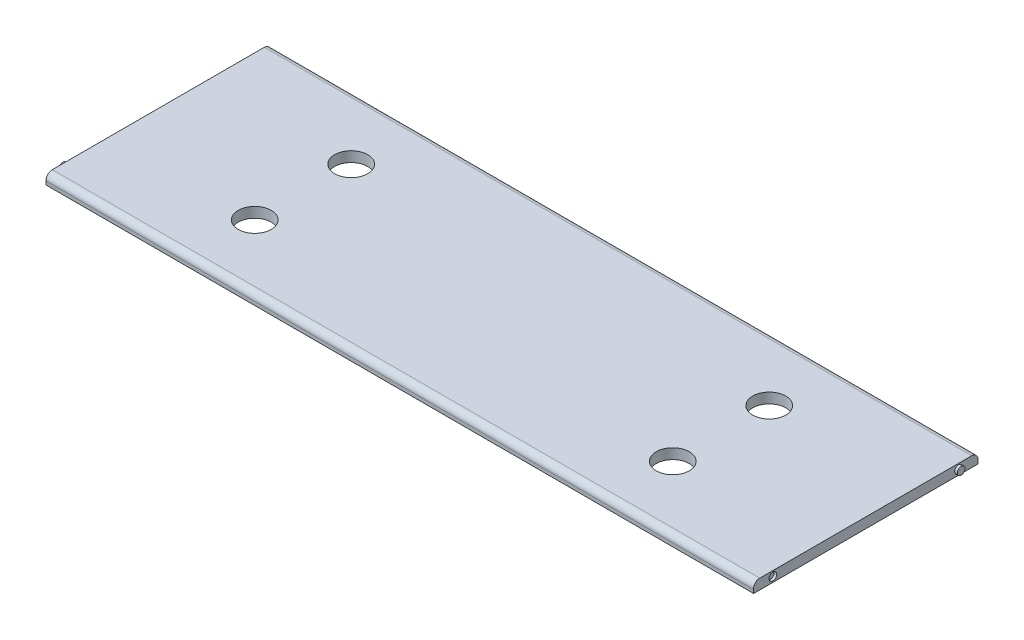
SolidWorks part; units mm, degrees
ref_plane "Front Plane" through (0, 0, 0) normal (0, 0, 1) x (1, 0, 0)
ref_plane "Top Plane" through (0, 0, 0) normal (0, 1, 0) x (1, 0, 0)
ref_plane "Right Plane" through (0, 0, 0) normal (1, 0, 0) x (0, 0, -1)
sketch "Sketch1" plane through (0, 0, 0) normal (0, 0, 1) x (1, 0, 0)
  line L0 (-247.65, 0) -> (247.65, 0) construction
  line L1 (0, 0) -> (0, 215.9) construction
  line L2 (69.85, 215.9) -> (-69.85, 215.9)
  line L3 (-247.65, 12.7) -> (-247.65, -12.7)
  line L4 (-247.65, -12.7) -> (-245.618, -12.7)
  line L5 (-245.618, -12.7) -> (-245.618, 12.7)
  line L6 (69.85, 213.868) -> (-69.85, 213.868)
  line L7 (247.65, 12.7) -> (247.65, -12.7)
  line L8 (247.65, -12.7) -> (245.618, -12.7)
  line L9 (245.618, -12.7) -> (245.618, 12.7)
  spline S0 degree 3 poles (-69.85, 215.9) (-159.8519, 215.9) (-247.65, 151.1387) (-247.65, 12.7) knots 0 0 0 0 1 1 1 1
  spline S1 degree 1 poles (-69.85, 213.868) (-245.618, 12.7) knots 0 0 1 1 construction
  spline S2 degree 3 poles (-69.85, 213.868) (-75.4039, 213.868) (-86.5291, 213.3675) (-108.5033, 210.3484) (-135.224, 202.7605) (-165.0781, 187.4572) (-187.3049, 169.4544) (-203.0081, 151.8427) (-213.6244, 137.0121) (-222.9564, 120.5424) (-230.8798, 102.4156) (-237.269, 82.6136) (-241.209, 64.7021) (-243.4667, 49.5177) (-244.6967, 37.7027) (-245.3224, 27.4898) (-245.5754, 19.121) (-245.618, 14.8317) (-245.618, 12.7) knots 0 0 0 0 0.0625 0.125 0.25 0.375 0.5 0.5625 0.625 0.6875 0.75 0.8125 0.875 0.90625 0.9375 0.96875 0.984375 1 1 1 1
  spline S3 degree 3 poles (247.65, 12.7) (247.65, 151.1387) (159.8519, 215.9) (69.85, 215.9) knots 0 0 0 0 1 1 1 1
  spline S4 degree 1 poles (245.618, 12.7) (69.85, 213.868) knots 0 0 1 1 construction
  spline S5 degree 3 poles (245.618, 12.7) (245.618, 14.8317) (245.5754, 19.121) (245.3224, 27.4898) (244.6967, 37.7027) (243.4667, 49.5177) (241.209, 64.7021) (237.269, 82.6136) (230.8798, 102.4156) (222.9564, 120.5424) (213.6244, 137.0121) (203.0081, 151.8427) (187.3049, 169.4544) (165.0781, 187.4572) (135.224, 202.7605) (108.5033, 210.3484) (86.5291, 213.3675) (75.4039, 213.868) (69.85, 213.868) knots 0 0 0 0 0.015625 0.03125 0.0625 0.09375 0.125 0.1875 0.25 0.3125 0.375 0.4375 0.5 0.625 0.75 0.875 0.9375 1 1 1 1
  point P18 (0, 213.868)
  dimension "D1" = 495.3
  dimension "D2" = 215.9
  dimension "D3" = 25.4
  dimension "D4" = 69.85
  dimension "D5" = 2.032
  dimension "D6" = 2.032
  dimension "D7" = 2.032
  dimension "D8" = 2.032
extrude "Boss-Extrude1" add sketch "Sketch1" along normal mid plane 44.45 contours S5 L9 L8 L7 S3 L2 S0 L3 L4 L5 S2 L6 region at (202.6354, 154.1572, 0)
sketch "Sketch2" plane through (0, 0, 0) normal (1, 0, 0) x (0, 0, -1)
  circle A0 centre (0, 0) radius 4.7625
  dimension "D1" = 9.525
extrude "Cut-Extrude1" cut sketch "Sketch2" against normal up to next and the other way up to next
sketch "Sketch3" plane through (0, 0, 0) normal (1, 0, 0) x (0, 0, -1)
  line L2 (-22.225, 215.9) -> (-12.7, -12.7)
  line L3 (-22.225, 215.9) -> (22.225, 215.9) construction
  line L4 (-12.7, -12.7) -> (12.7, -12.7) construction
  line L5 (22.225, 215.9) -> (12.7, -12.7)
  line L6 (-22.225, 215.9) -> (-47.625, 215.9)
  line L7 (-47.625, 215.9) -> (-47.625, -12.7)
  line L8 (-47.625, -12.7) -> (-12.7, -12.7)
  line L9 (22.225, 215.9) -> (47.625, 215.9)
  line L10 (47.625, 215.9) -> (47.625, -12.7)
  line L11 (47.625, -12.7) -> (12.7, -12.7)
  line L12 (0, 0) -> (0, -12.7) construction
  line L13 (-22.225, -12.7) -> (22.225, -12.7) construction
  dimension "D1" = 25.4
  dimension "D3" = 25.4
extrude "Cut-Extrude2" cut sketch "Sketch3" against normal mid plane 508
fillet "Fillet1" radius 12.7 4 edges at (-246.634, -12.7, -12.7) (-246.634, -12.7, 12.7) (246.634, -12.7, -12.7) (246.634, -12.7, 12.7)
ref_axis "Wheel Axis" through (-328.0677, 0, 0) along (1, 0, 0)
fillet "Fillet4" radius 1.2446 16 edges at (247.65, -9.1653, -9.3095) (247.65, 6.0856, -13.4827) (-247.65, -9.1653, -9.3095) (-247.65, 6.0856, -13.4827) (247.65, -9.1653, 9.3095) (247.65, 6.0856, 13.4827) (-247.65, -9.1653, 9.3095) (-247.65, 6.0856, 13.4827) (0, 215.9, 22.225) (-207.2038, 149.2346, 19.4473) (-247.65, -12.7, 0) (-180.307, 177.3414, -20.6184) (0, 215.9, -22.225) (207.2038, 149.2346, -19.4473) (247.65, -12.7, 0) (180.307, 177.3414, 20.6184)
hole_wizard "1/4 Clearance Hole1" positions "Sketch5" profile "Sketch4" hole size "1/4" standard "ANSI Inch"
sketch "Sketch5" plane through (5.7342, 215.9, -6.6588) normal (0, 1, 0) x (1, 0, 0)
  line L0 (64.1158, -6.6588) -> (-75.5842, -6.6588) construction
  line L4 (-5.7342, -27.5863) -> (-5.7342, 14.2686) construction
  line L7 (64.1158, -27.5863) -> (64.1158, 14.2686) construction
  line L8 (-75.5842, -27.5863) -> (-75.5842, 14.2686) construction
  line L9 (-75.5842, -27.5863) -> (64.1158, -27.5863) construction
  line L10 (64.1158, 14.2686) -> (-75.5842, 14.2686) construction
  point P0 (35.5408, -16.1838)
  point P2 (35.5408, 2.8662)
  point P4 (-47.0092, -16.1838)
  point P6 (-47.0092, 2.8662)
  dimension "D1" = 82.55
  dimension "D2" = 9.525
  dimension "D3" = 9.525
sketch "Sketch4" plane through (41.275, 215.9, 9.525) normal (1, 0, 0) x (0, 0, 1)
  line L0 (0, 0) -> (0, 8.3111)
  line L1 (0, 8.3111) -> (3.2639, 6.35)
  line L2 (3.2639, 6.35) -> (3.2639, 0)
  line L5 (3.2639, 0) -> (0, 0)
  line L10 (0, 8.3111) -> (-3.2639, 6.35) construction
  line L11 (0, -6.35) -> (0, 107.95) construction
  dimension "Hole Dia." = 6.5278
  dimension "Hole Depth" = 6.35
  dimension "Drill Angle" = 118
ref_plane "Plane1" through (69.85, 0, 0) normal (-1, 0, 0) x (0, 0, 1)
sketch "Sketch6" plane through (69.85, 0, 0) normal (-1, 0, 0) x (0, 0, 1)
  line L1 (30.2308, 222.1338) -> (-35.3786, 222.1338)
  line L2 (30.2308, 222.1338) -> (30.2308, -24.054)
  line L3 (30.2308, -24.054) -> (-35.3786, -24.054)
  line L4 (-35.3786, 222.1338) -> (-35.3786, -24.054)
extrude "Cut-Extrude3" cut sketch "Sketch6" against normal blind 200.66
ref_plane "Plane2" through (-69.85, 0, 0) normal (-1, 0, 0) x (0, 0, 1)
sketch "Sketch7" plane through (-69.85, 0, 0) normal (-1, 0, 0) x (0, 0, 1)
  line L1 (-27.4788, 230.8864) -> (26.4161, 230.8864)
  line L2 (-27.4788, 230.8864) -> (-27.4788, -46.2018)
  line L3 (-27.4788, -46.2018) -> (26.4161, -46.2018)
  line L4 (26.4161, 230.8864) -> (26.4161, -46.2018)
extrude "Cut-Extrude4" cut sketch "Sketch7" along normal blind 200.66
sketch "Sketch8" plane through (69.85, 0, 0) normal (1, 0, 0) x (0, 0, -1)
  line L0 (-20.9275, 215.9) -> (20.9275, 215.9) construction
  circle A0 centre (18.3303, 214.884) radius 0.762
  dimension "D1" = 1.524
  dimension "D2" = 1.016
  dimension "D3" = 3.81
extrude "Boss-Extrude2" add sketch "Sketch8" along normal blind 0.508
sketch "Sketch9" plane through (69.85, 0, 0) normal (1, 0, 0) x (0, 0, -1)
  line L0 (-20.9275, 215.9) -> (20.9275, 215.9) construction
  circle A0 centre (-18.3303, 214.884) radius 0.762
  dimension "D1" = 1.524
  dimension "D2" = 1.016
  dimension "D3" = 3.81
extrude "Cut-Extrude5" cut sketch "Sketch9" against normal blind 0.508
sketch "Sketch10" plane through (-69.85, 0, 0) normal (-1, 0, 0) x (0, 0, 1)
  line L0 (20.9275, 215.9) -> (-20.9275, 215.9) construction
  circle A0 centre (-18.3303, 214.884) radius 0.762
  dimension "D1" = 1.524
  dimension "D2" = 1.016
  dimension "D3" = 3.81
extrude "Cut-Extrude6" cut sketch "Sketch10" against normal blind 0.508
sketch "Sketch11" plane through (-69.85, 0, 0) normal (-1, 0, 0) x (0, 0, 1)
  line L0 (20.9275, 215.9) -> (-20.9275, 215.9) construction
  circle A0 centre (18.3303, 214.884) radius 0.762
  dimension "D1" = 1.524
  dimension "D2" = 1.016
  dimension "D3" = 3.81
extrude "Boss-Extrude3" add sketch "Sketch11" along normal blind 0.508
